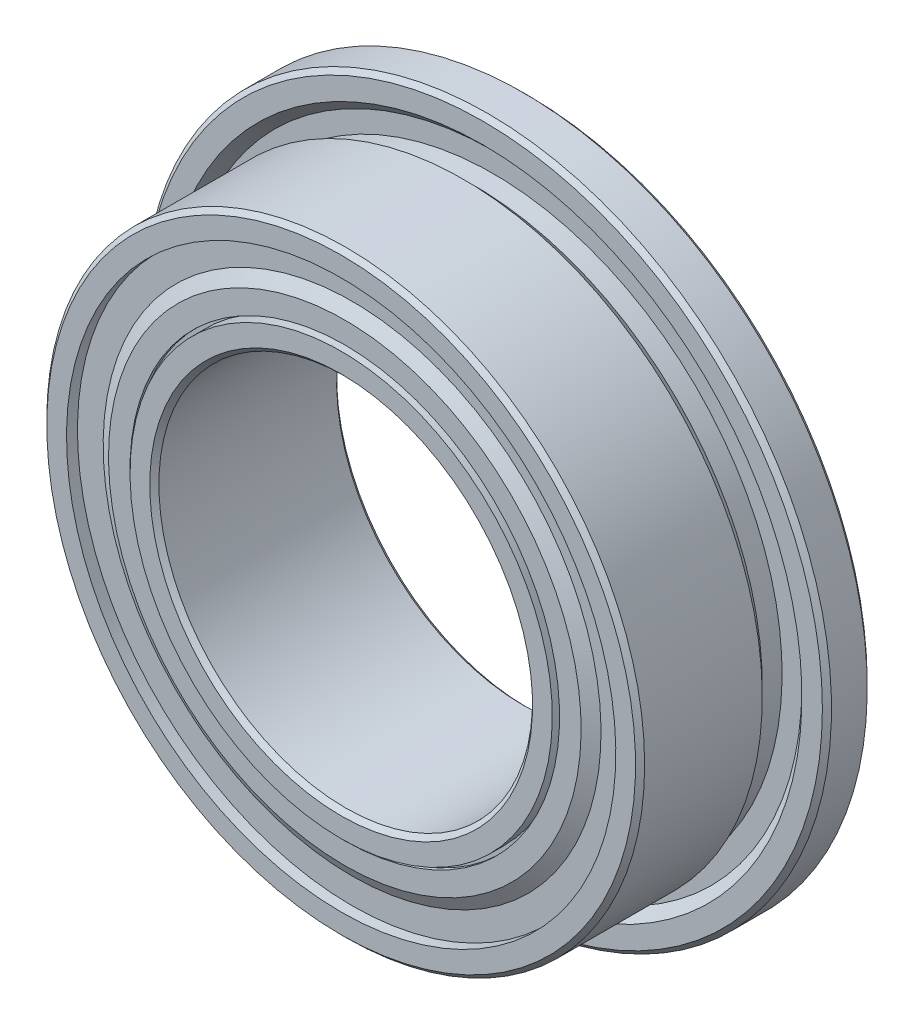
SolidWorks part; units mm, degrees
ref_plane "Front Plane" through (0, 0, 0) normal (0, 0, 1) x (1, 0, 0)
ref_plane "Top Plane" through (0, 0, 0) normal (0, 1, 0) x (1, 0, 0)
ref_plane "Right Plane" through (0, 0, 0) normal (1, 0, 0) x (0, 0, -1)
sketch "Sketch1" plane through (0, 0, 0) normal (1, 0, 0) x (0, 0, -1)
  line L0 (0, 4) -> (0, -4) construction
  line L1 (-1.25, 4) -> (1.25, 4) construction
  line L2 (0, 0) -> (1.25, 0) construction
  line L3 (1.25, 4.6) -> (1.25, -4.6) construction
  line L4 (1.25, -4.6) -> (0.65, -4.6) construction
  line L5 (1.25, 2.5) -> (0, 2.5) construction
  line L6 (1.25, 2.5) -> (1.25, -2.5) construction
  dimension "OD" = 8
  dimension "Width" = 2.5
  dimension "Flange Thickness" = 0.6
  dimension "ID" = 5
  dimension "Flange OD" = 9.2
sketch "Sketch2" plane through (0, 0, 0) normal (1, 0, 0) x (0, 0, -1)
  line L0 (1.25, 4.6) -> (0.65, 4.6)
  line L1 (0.65, 4.6) -> (0.65, 4.2652)
  line L2 (0.3848, 4) -> (-1.25, 4)
  line L3 (-1.25, 4) -> (-1.25, 3.5125)
  line L4 (-1.25, 3.5125) -> (-0.3018, 3.5125)
  line L5 (1.25, 4.6) -> (1.25, -4.6) construction
  line L6 (1.25, 3.5125) -> (1.25, 4.6)
  line L7 (1.25, 2.5) -> (-1.25, 2.5)
  line L8 (-1.25, 2.5) -> (-1.25, 2.9875)
  line L9 (-1.25, 2.9875) -> (-0.3018, 2.9875)
  line L10 (1.25, 2.9875) -> (1.25, 2.5)
  line L11 (0, 4) -> (0, 2.5) construction
  line L12 (-0.4, 3.25) -> (0.4, 3.25) construction
  line L13 (0.3018, 3.5125) -> (1.25, 3.5125)
  line L14 (0.3018, 2.9875) -> (1.25, 2.9875)
  line L15 (0.65, 4.2652) -> (0.7826, 4.1326)
  line L16 (0.7826, 4.1326) -> (0.7826, 3.8674)
  line L17 (0.7826, 3.8674) -> (0.5174, 3.8674)
  line L18 (0.5174, 3.8674) -> (0.3848, 4)
  line L19 (0.65, 4) -> (0.7826, 3.8674) construction
  line L20 (0.7826, 4.1326) -> (0.5174, 3.8674) construction
  line L21 (0.3848, 4) -> (0.65, 4) construction
  line L22 (0.65, 4) -> (0.65, 4.2652) construction
  line L23 (-1.25, 0) -> (1.25, 0) construction
  circle A0 centre (0, 3.25) radius 0.4 construction
  arc A1 (-0.3018, 3.5125) -> (0.3018, 3.5125) centre (0, 3.25) cw
  arc A2 (-0.3018, 2.9875) -> (0.3018, 2.9875) centre (0, 3.25) ccw
  dimension "Ball Dia." = 0.8
  dimension "D2" = 135
  dimension "D3" = 0.375
  dimension "Race Thikness" = 0.4875
  dimension "D4" = 0.525
revolve "Revolve1" add sketch "Sketch2" angle 360 about L2
fillet "Fillet1" radius 0.0609 3 edges at (0, -4.6, -1.25) (0, -4.6, -0.65) (0, -4, 1.25) profile chamfer
sketch "Sketch3" plane through (0, 0, 0) normal (0, 0, 1) x (1, 0, 0)
  line L0 (-2.5, 0) -> (2.5, 0) construction
  line L1 (-4, 0) -> (4, 0) construction
  point P5 (0, 0)
  dimension "ID2" = 5
  dimension "OD2" = 8
fillet "Fillet2" radius 0.0609 2 edges at (0, -2.5, -1.25) (0, -2.5, 1.25) profile chamfer
sketch "Sketch7" plane through (0, 0, 0) normal (0, 0, 1) x (1, 0, 0)
  line L0 (0, 3.65) -> (0, 2.85)
  line L1 (0, 4.6) -> (0, -4.6) construction
  line L2 (-0.4527, 3.65) -> (0, 0) construction
  line L3 (0, 0) -> (0.4527, 3.65) construction
  line L4 (0.4527, 3.65) -> (-0.4527, 3.65) construction
  circle A0 centre (0, 3.25) radius 0.4 construction
  circle A1 centre (0, 0) radius 3.65 construction
  circle A2 centre (0, 0) radius 2.85 construction
  arc A4 (0, 3.65) -> (0, 2.85) centre (0, 3.25) ccw
  dimension "D1" = 14.139
revolve "Revolve3" add sketch "Sketch7" angle 360 about L0
pattern_circular "CirPattern3" count 21 over 360 about axis through (0, 0, 0) along (0, 0, -1) of bodies 107
sketch "Sketch8" plane through (0, 0, 0) normal (1, 0, 0) x (0, 0, -1)
  line L1 (-1.25, 3.5125) -> (-1.055, 3.5125)
  line L2 (-1.25, 3.5125) -> (-1.25, 3.675)
  line L3 (-1.25, 3.675) -> (-1.055, 3.675)
  line L4 (-1.055, 3.5125) -> (-1.055, 3.675)
  line L5 (1.25, 3.5125) -> (1.055, 3.5125)
  line L6 (1.25, 3.5125) -> (1.25, 3.675)
  line L7 (1.25, 3.675) -> (1.055, 3.675)
  line L8 (1.055, 3.5125) -> (1.055, 3.675)
  line L9 (1.25, 2.9875) -> (1.055, 2.9875)
  line L10 (1.25, 2.9875) -> (1.25, 2.825)
  line L11 (1.25, 2.825) -> (1.055, 2.825)
  line L12 (1.055, 2.9875) -> (1.055, 2.825)
  line L13 (-1.25, 2.9875) -> (-1.055, 2.9875)
  line L14 (-1.25, 2.9875) -> (-1.25, 2.825)
  line L15 (-1.25, 2.825) -> (-1.055, 2.825)
  line L16 (-1.055, 2.9875) -> (-1.055, 2.825)
  dimension "D1" = 0.1625
  dimension "D2" = 0.195
revolve "Cut-Revolve1" cut sketch "Sketch8" angle 360 about L2
sketch "Sketch9" plane through (0, 0, 0) normal (1, 0, 0) x (0, 0, -1)
  line L0 (-1.055, 3.675) -> (-1.055, 3.3179)
  line L1 (-1.055, 3.3179) -> (-1.1525, 3.149)
  line L2 (-1.1525, 3.149) -> (-1.1525, 2.8737)
  line L3 (1.1525, 2.8737) -> (1.1525, 2.825) construction
  line L4 (1.055, 3.675) -> (1.055, 3.3179)
  line L5 (1.055, 3.3179) -> (1.1525, 3.149)
  line L6 (1.1525, 3.149) -> (1.1525, 2.8737)
  line L7 (1.25, 2.825) -> (1.055, 2.825) construction
  line L8 (-1.1037, 3.675) -> (-1.1037, 3.3309)
  line L9 (-1.1037, 3.3309) -> (-1.2013, 3.162)
  line L10 (-1.2013, 3.162) -> (-1.2013, 2.8737)
  line L11 (-1.055, 3.675) -> (-1.1037, 3.675)
  line L12 (-1.1525, 2.8737) -> (-1.2013, 2.8737)
  line L13 (1.1038, 3.675) -> (1.1038, 3.3309)
  line L14 (1.1038, 3.3309) -> (1.2013, 3.162)
  line L15 (1.2013, 3.162) -> (1.2013, 2.8737)
  line L16 (1.055, 3.675) -> (1.1038, 3.675)
  line L17 (1.1525, 2.8737) -> (1.2013, 2.8737)
  line L18 (-1.055, 3.3179) -> (-1.055, 2.5308) construction
  line L19 (1.055, 3.3179) -> (1.055, 3.675) construction
  line L20 (-1.055, 2.825) -> (-1.25, 2.825) construction
  line L22 (-1.1525, 2.8737) -> (-1.1525, 2.825) construction
  dimension "D2" = 150
  dimension "D1" = 150
  dimension "D5" = 0.195
  dimension "D3" = 0.0488
  dimension "D4" = 0.0488
  dimension "D6" = 0.3571
revolve "Revolve4" add sketch "Sketch9" angle 360 about L2
equation "\"D1@Fillet1\"=\"Race Thikness@Sketch2\"/8"
equation "\"ID2@Sketch3\" = \"ID@Sketch1\""
equation "\"OD2@Sketch3\" = \"OD@Sketch1\""
equation "\"D1@Fillet2\"=\"Race Thikness@Sketch2\"/8"
equation "\"D1@CirPattern3\"=360/\"D1@Sketch7\"-4"
equation "\"D1@Sketch8\"=\"Race Thikness@Sketch2\"/3"
equation "\"D2@Sketch8\"=\"Race Thikness@Sketch2\"/2.5"
equation "\"D3@Sketch9\"=\"D5@Sketch9\"/4"
equation "\"D4@Sketch9\"=\"D5@Sketch9\"/4"
equation "\"D1@Sketch9\"=\"D2@Sketch9\""
equation "\"Ball Dia.@Sketch2\" = \"D1@Sketch2\"*.5"
equation "\"D4@Sketch2\"=((\"OD@Sketch1\"-\"ID@Sketch1\")/2)*.35"
